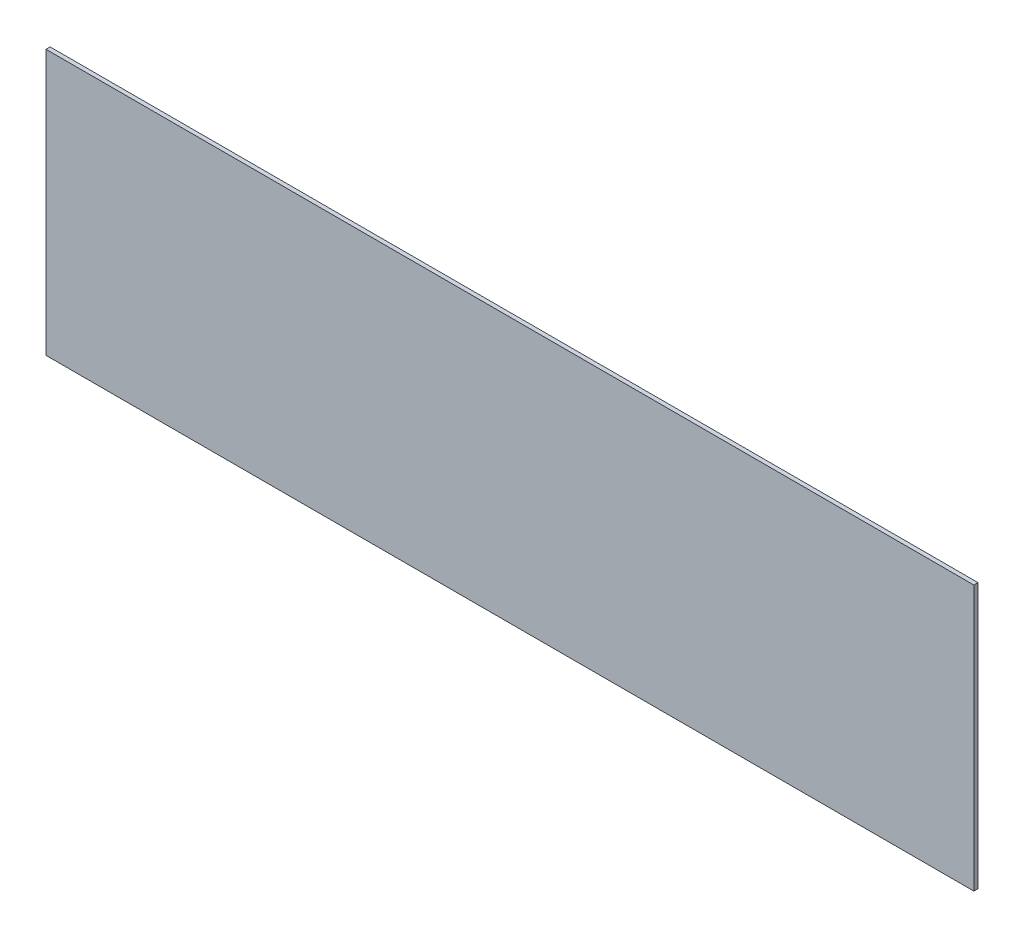
SolidWorks part; units mm, degrees
ref_plane "Front Plane" through (0, 0, 0) normal (0, 0, 1) x (1, 0, 0)
ref_plane "Top Plane" through (0, 0, 0) normal (0, 1, 0) x (1, 0, 0)
ref_plane "Right Plane" through (0, 0, 0) normal (1, 0, 0) x (0, 0, -1)
sketch "Sketch1" plane through (0, 0, 0) normal (0, 0, 1) x (1, 0, 0)
  line L1 (0, 0) -> (711.2, 0)
  line L2 (0, 0) -> (0, 203.2)
  line L3 (0, 203.2) -> (711.2, 203.2)
  line L4 (711.2, 0) -> (711.2, 203.2)
  dimension "D1" = 203.2
  dimension "D2" = 711.2
extrude "Boss-Extrude1" add sketch "Sketch1" along normal blind 3.175
